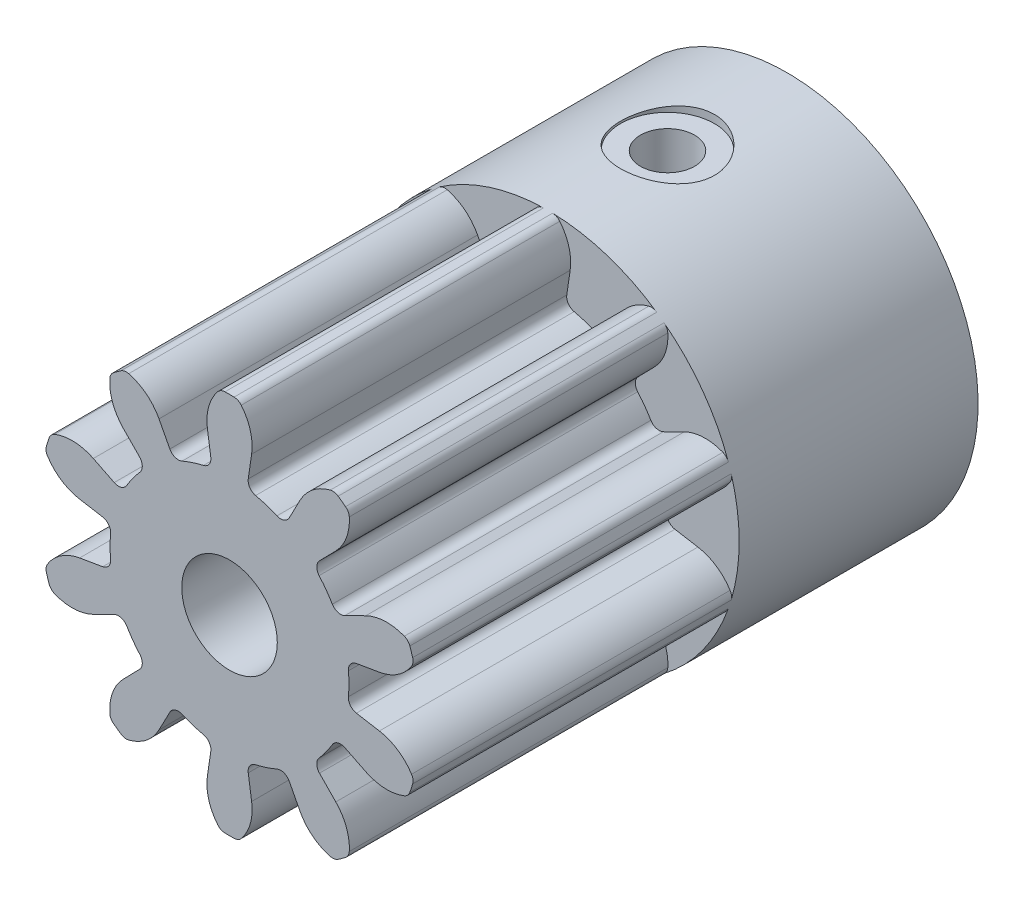
SolidWorks part; units mm, degrees
ref_plane "Front Plane" through (0, 0, 0) normal (0, 0, 1) x (1, 0, 0)
ref_plane "Top Plane" through (0, 0, 0) normal (0, 1, 0) x (1, 0, 0)
ref_plane "Right Plane" through (0, 0, 0) normal (1, 0, 0) x (0, 0, -1)
sketch "DiametrosPiñon" plane through (0, 0, 0) normal (0, 0, 1) x (1, 0, 0)
  circle A27 centre (0, 0) radius 10 construction
  circle A28 centre (0, 0) radius 12 construction
  circle A43 centre (0, 0) radius 7.5 construction
  circle A49 centre (0, 0) radius 12 construction
  dimension "Dp" = 20
  dimension "Di" = 15
  dimension "De" = 24
sketch "Pinon-Machote" plane through (0, 0, 0) normal (0, 0, 1) x (1, 0, 0)
  line L0 (0, 0) -> (0, 12) construction
  line L1 (0, 0) -> (1.8772, 11.8523) construction
  line L2 (0, 0) -> (-1.8772, 11.8523) construction
  line L3 (0, 0) -> (-1.835, 12.4799)
  circle A27 centre (0, 0) radius 10
  circle A28 centre (0, 0) radius 12 construction
  circle A36 centre (-1.5643, 9.8769) radius 2.9845 construction
  circle A37 centre (1.5643, 9.8769) radius 2.9845 construction
  circle A43 centre (0, 0) radius 7.5
  circle A46 centre (1.5643, 9.8769) radius 2.9845
  circle A47 centre (-1.5643, 9.8769) radius 2.9845 construction
  circle A49 centre (0, 0) radius 12
  circle A50 centre (-0.273, 11.3967) radius 0.6
  circle A52 centre (-1.7687, 7.9045) radius 0.6
  circle A53 centre (-1.4201, 9.8987) radius 0.0462
  circle A54 centre (1.4201, 9.8987) radius 0.0083
  dimension "De" = 24
  dimension "Dp" = 20
  dimension "Di" = 15
  dimension "Paso1_95%" = 5.969
  dimension "Paso2_95%" = 5.969
  dimension "filet3" = 1.2
  dimension "Filet1" = 1.2
  dimension "(360/N)/4 Angulo1" = 9
  dimension "(360/N)/4 Angulo2" = 9
  dimension "D1" = 0.635
  dimension "D2" = 0.1459
  dimension "D3" = 2.8402
  dimension "D4" = 3.1287
sketch "Arco" plane through (0, 0, 0) normal (0, 0, 1) x (1, 0, 0)
  line L0 (0, 0) -> (0, 12) construction
  line L1 (0, 0) -> (1.8772, 11.8523) construction
  line L2 (0, 0) -> (-1.8772, 11.8523) construction
  line L3 (0, 0) -> (-2.4289, 16.519) construction
  circle A27 centre (0, 0) radius 10 construction
  circle A28 centre (0, 0) radius 12 construction
  circle A36 centre (-1.5643, 9.8769) radius 2.9845 construction
  circle A37 centre (1.5643, 9.8769) radius 2.9845 construction
  circle A43 centre (0, 0) radius 7.5
  circle A46 centre (1.5643, 9.8769) radius 2.9845 construction
  circle A47 centre (-1.5643, 9.8769) radius 2.9845 construction
  circle A49 centre (0, 0) radius 12 construction
  circle A50 centre (-0.273, 11.3967) radius 0.6 construction
  circle A52 centre (-1.7687, 7.9045) radius 0.6 construction
  circle A53 centre (0, 0) radius 3
  dimension "D1" = 0.635
  dimension "De" = 24
  dimension "Di" = 15
  dimension "Dp" = 20
  dimension "D2" = 6
  dimension "Paso1_95%" = 5.969
  dimension "Paso2_95%" = 5.969
  dimension "Filet1" = 1.2
  dimension "filet3" = 1.2
  dimension "(360/N)/4 Angulo1" = 9
  dimension "(360/N)/4 Angulo2" = 9
sketch "Diente" plane through (0, 0, 0) normal (0, 0, 1) x (1, 0, 0)
  line L6 (-1.1751, 7.9918) -> (-1.3884, 9.4427)
  line L8 (1.1751, 7.9918) -> (1.3884, 9.4427)
  arc A37 (-0.7354, 11.7792) -> (-1.3884, 9.4427) centre (1.5643, 9.8769) ccw construction
  arc A43 (1.6377, 7.319) -> (-1.6377, 7.319) centre (0, 0) ccw
  arc A46 (-0.7354, 11.7792) -> (-1.3884, 9.4427) centre (1.5643, 9.8769) ccw
  arc A52 (-1.6377, 7.319) -> (-1.1751, 7.9918) centre (-1.7687, 7.9045) ccw
  arc A53 (1.6377, 7.319) -> (1.1751, 7.9918) centre (1.7687, 7.9045) cw
  arc A54 (0.2874, 11.9966) -> (0.7354, 11.7792) centre (0.273, 11.3967) cw
  arc A55 (-0.2874, 11.9966) -> (-0.7354, 11.7792) centre (-0.273, 11.3967) ccw
  arc A56 (0.2874, 11.9966) -> (-0.2874, 11.9966) centre (0, 0) ccw construction
  arc A57 (0.2874, 11.9966) -> (-0.2874, 11.9966) centre (0, 0) ccw
  arc A61 (1.3884, 9.4427) -> (0.7354, 11.7792) centre (-1.5643, 9.8769) ccw
  arc A62 (1.3884, 9.4427) -> (0.7354, 11.7792) centre (-1.5643, 9.8769) ccw construction
  dimension "Di" = 15
  dimension "Paso2_95%" = 5.969
  dimension "Filet1" = 1.2
extrude "Extrude-Arco" add sketch "Arco" along normal blind 10 and the other way blind 10
extrude "Extrude-Diente" add sketch "Diente" along normal blind 10 and the other way blind 10 contours A43 A52 L6 A46 A55 A57 A54 A61 L8 A53
pattern_circular "CirPattern2" count 10 over 360 about axis through (0, 0, 10) along (0, 0, 1) of "Extrude-Diente"
sketch "Sketch1" plane through (0, 0, -10) normal (0, 0, -1) x (-1, 0, 0)
  circle A0 centre (0, 0) radius 12
  circle A1 centre (0, 0) radius 3
extrude "Boss-Extrude1" add sketch "Sketch1" along normal blind 15
sketch "Sketch2" plane through (0, 0, 0) normal (1, 0, 0) x (0, 0, -1)
  line L0 (10, 14.2453) -> (10, -15.4471) construction
  line L1 (16.9435, -12) -> (28.4259, -12)
  line L2 (25, 14.2453) -> (25, -14.9522) construction
  line L3 (25, -12) -> (25, 12) construction
  line L4 (0, 0) -> (33.6465, 0) construction
  line L5 (17.5, -12.7433) -> (17.5, 13.586) construction
  line L6 (14.5988, -1.675) -> (20.4012, 1.675) construction
  line L7 (20.4012, -1.675) -> (14.5988, 1.675) construction
  line L8 (17.5, 3.35) -> (14.5988, 1.675)
  line L9 (14.5988, 1.675) -> (14.5988, -1.675)
  line L10 (14.5988, -1.675) -> (17.5, -3.35)
  line L11 (17.5, -3.35) -> (20.4012, -1.675)
  line L12 (20.4012, -1.675) -> (20.4012, 1.675)
  line L13 (20.4012, 1.675) -> (17.5, 3.35)
  line L14 (17.5, 3.35) -> (25.5, 3.35)
  line L15 (25.5, 3.35) -> (25.5, -3.35)
  line L16 (25.5, -3.35) -> (17.5, -3.35)
  line L18 (12.284, -7.5) -> (27.2195, -7.5)
  line L19 (-10, -12) -> (25, -12) construction
  line L22 (12.8457, -3.75) -> (30.8827, -3.75)
  line L23 (25.5, -10.85) -> (25.5, -4.15)
  line L24 (17.5, -10.85) -> (25.5, -10.85)
  line L25 (17.5, -10.85) -> (14.5988, -9.175)
  line L26 (14.5988, -9.175) -> (14.5988, -5.825)
  line L27 (14.5988, -5.825) -> (17.5, -4.15)
  line L28 (25.5, -4.15) -> (17.5, -4.15)
  circle A0 centre (17.5, 0) radius 3.35 construction
  dimension "D3" = 6.7
  dimension "D1" = 15
  dimension "D2" = 7.5
  dimension "D4" = 60
  dimension "D5" = 60
  dimension "D6" = 8
  dimension "D7" = 4.5
  dimension "D8" = 7.5
  dimension "D9" = 3.75
  dimension "D10" = 7.5
ref_plane "Plane1" through (0, 7.4, 0) normal (0, 1, 0) x (1, 0, 0)
sketch "Sketch3" plane through (0, 7.4, 0) normal (0, 1, 0) x (1, 0, 0)
  line L0 (0, 0) -> (0, 26.2095) construction
  line L1 (-9.6583, 17.5) -> (10.3249, 17.5) construction
  line L2 (12, 25) -> (-12, 25) construction
  line L3 (-1.675, 20.4012) -> (1.675, 14.5988) construction
  line L4 (-1.675, 14.5988) -> (1.675, 20.4012) construction
  line L5 (-1.675, 20.4012) -> (-3.35, 17.5)
  line L6 (-3.35, 17.5) -> (-1.675, 14.5988)
  line L7 (-1.675, 14.5988) -> (1.675, 14.5988)
  line L8 (-1.675, 20.4012) -> (1.675, 20.4012)
  line L9 (1.675, 20.4012) -> (3.35, 17.5)
  line L10 (3.35, 17.5) -> (1.675, 14.5988)
  line L11 (-3.35, 17.5) -> (-3.35, 26.5061)
  line L12 (-3.35, 26.5061) -> (3.35, 26.5061)
  line L13 (3.35, 26.5061) -> (3.35, 17.5)
  circle A0 centre (0, 17.5) radius 3.35 construction
  dimension "D2" = 6.7
  dimension "D1" = 7.5
  dimension "D3" = 60
  dimension "D4" = 60
extrude "Cut-Extrude1" cut sketch "Sketch3" against normal blind 1.5 and the other way blind 1.5 contours L10 L9 L8 L5 L6 L7 | L13 L12 L11 L5 L8 L9 region at (0, 7.4, -17.5) region at (0, 7.4, -23.0268)
sketch "Sketch4" plane through (0, 7.4, 0) normal (0, 1, 0) x (1, 0, 0)
  line L0 (-3.35, 25) -> (3.35, 25) construction
  circle A0 centre (0, 17.5) radius 1.7
  dimension "D1" = 3.4
  dimension "D2" = 7.5
extrude "Cut-Extrude2" cut sketch "Sketch4" against normal blind 6.5 and the other way blind 10
ref_plane "Plane2" through (0, 12, 0) normal (0, 1, 0) x (1, 0, 0)
sketch "Sketch5" plane through (0, 12, 0) normal (0, 1, 0) x (1, 0, 0)
  circle A0 centre (0, 17.5) radius 2.95
  dimension "D1" = 5.9
extrude "Cut-Extrude3" cut sketch "Sketch5" against normal blind 0.5
equation "\"ND\"= 10'Dientes"
equation "\"PD\"= 0.5'Dientes/mm pero 12.7 dientes/pulg"
equation "\"D\"= \"ND\" / \"PD\"'diam. paso"
equation "\"p\"= ( PI * \"D\" ) / \"ND\"'paso circular"
equation "\"m\"= 1 / \"PD\"'modulo"
equation "\"a\"= 1 / \"PD\"'addendum"
equation "\"b\"= 1.25 / \"PD\"'Pie del diente o dedendum"
equation "\"ht\"= \"a\" + \"b\"'Altura del diente"
equation "\"c\"= \"b\" - \"a\"'Claro del diete"
equation "\"t\"= PI / ( 2 * \"PD\" )'Espesor del diente"
equation "\"De\"= \"D\" + ( 2 * \"a\" )'Diam. Externo"
equation "\"Di\"= \"D\" - ( 2 * \"b\" )'Diam. Interno"
equation "\"r\"= 0.3 * \"m\"'radio de filete"
equation "\"Espesor-Corona\"= 6 + ( 6 * 2 )'Espesor despues del De"
equation "\"Deje\"= 6'Diam. Motor"
equation "\"Di@Pinon-Machote\" = \"Di\""
equation "\"(360/N)/4 Angulo1@Pinon-Machote\" =  ( 360 / \"ND\" )  / 4"
equation "\"(360/N)/4 Angulo2@Pinon-Machote\" =  ( 360 / \"ND\" )  / 4"
equation "\"Paso1_95%@Pinon-Machote\" = \"p\" * 0.95"
equation "\"Paso2_95%@Pinon-Machote\" = \"p\" * 0.95"
equation "\"filet3@Pinon-Machote\" = \"r\" * 2"
equation "\"Filet1@Pinon-Machote\"=\"r\"*2"
equation "\"De@DiametrosPiñon\" = \"De\""
